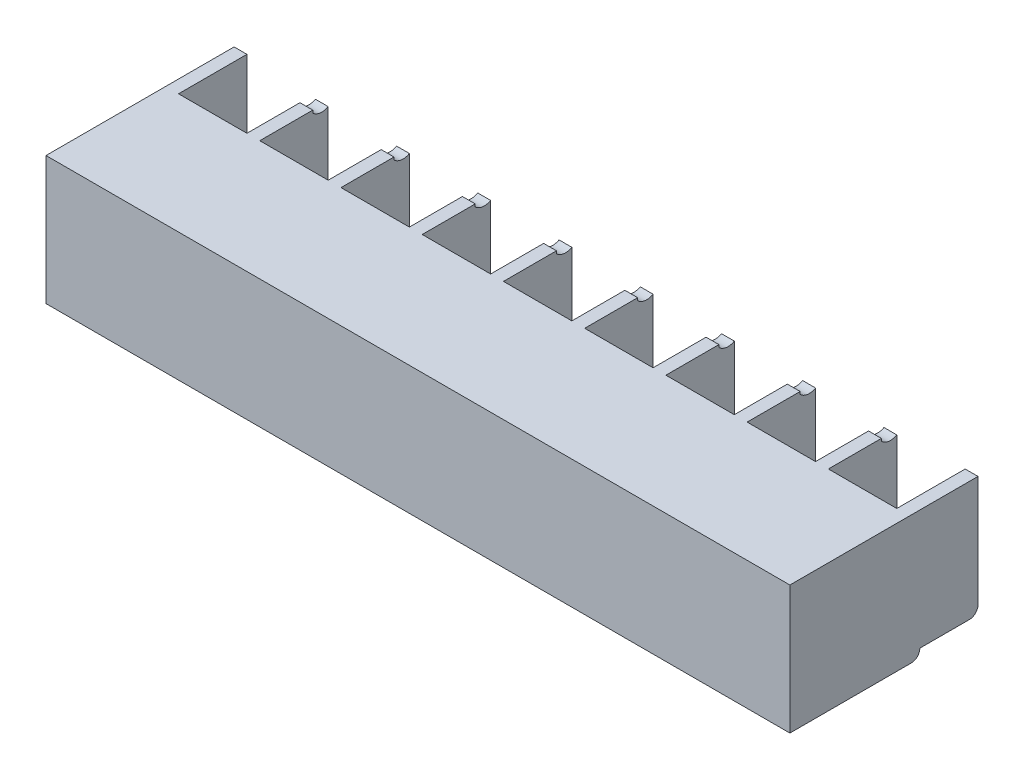
SolidWorks part; units mm, degrees
ref_plane "Спереди" through (0, 0, 0) normal (0, 0, 1) x (1, 0, 0)
ref_plane "Сверху" through (0, 0, 0) normal (0, 1, 0) x (1, 0, 0)
ref_plane "Справа" through (0, 0, 0) normal (1, 0, 0) x (0, 0, -1)
sketch "Эскиз1" plane through (0, 0, 0) normal (0, 0, 1) x (1, 0, 0)
  line L1 (-43.5, -7.5) -> (43.5, -7.5)
  line L2 (-43.5, -7.5) -> (-43.5, 7.5)
  line L3 (-43.5, 7.5) -> (43.5, 7.5)
  line L4 (43.5, -7.5) -> (43.5, 7.5)
  line L5 (-43.5, -7.5) -> (43.5, 7.5) construction
  line L6 (-43.5, 7.5) -> (43.5, -7.5) construction
  point P0 (0, 0)
  dimension "D1" = 87
  dimension "D2" = 15
extrude "Бобышка-Вытянуть1" add sketch "Эскиз1" along normal blind 22
sketch "Эскиз2" plane through (0, 0, 0) normal (0, 0, -1) x (-1, 0, 0)
  line L0 (-42, 7.5) -> (-42, -7.5)
  line L1 (-43.5, 7.5) -> (43.5, 7.5) construction
  line L2 (43.5, -7.5) -> (-43.5, -7.5) construction
  line L3 (-42, -7.5) -> (-34, -7.5)
  line L4 (-34, -7.5) -> (-34, 7.5)
  line L5 (-34, 7.5) -> (-42, 7.5)
  line L6 (-43.5, -7.5) -> (-43.5, 7.5) construction
  line L7 (-32.5, 7.5) -> (-32.5, -7.5)
  line L8 (-24.5, -7.5) -> (-24.5, 7.5)
  line L9 (-24.5, 7.5) -> (-32.5, 7.5)
  line L10 (-32.5, -7.5) -> (-24.5, -7.5)
  line L11 (-23, 7.5) -> (-23, -7.5)
  line L12 (-15, -7.5) -> (-15, 7.5)
  line L13 (-15, 7.5) -> (-23, 7.5)
  line L14 (-23, -7.5) -> (-15, -7.5)
  line L15 (-13.5, 7.5) -> (-13.5, -7.5)
  line L16 (-5.5, -7.5) -> (-5.5, 7.5)
  line L17 (-5.5, 7.5) -> (-13.5, 7.5)
  line L18 (-13.5, -7.5) -> (-5.5, -7.5)
  line L19 (-4, 7.5) -> (-4, -7.5)
  line L20 (4, -7.5) -> (4, 7.5)
  line L21 (4, 7.5) -> (-4, 7.5)
  line L22 (-4, -7.5) -> (4, -7.5)
  line L23 (5.5, 7.5) -> (5.5, -7.5)
  line L24 (13.5, -7.5) -> (13.5, 7.5)
  line L25 (13.5, 7.5) -> (5.5, 7.5)
  line L26 (5.5, -7.5) -> (13.5, -7.5)
  line L27 (15, 7.5) -> (15, -7.5)
  line L28 (23, -7.5) -> (23, 7.5)
  line L29 (23, 7.5) -> (15, 7.5)
  line L30 (15, -7.5) -> (23, -7.5)
  line L31 (24.5, 7.5) -> (24.5, -7.5)
  line L32 (32.5, -7.5) -> (32.5, 7.5)
  line L33 (32.5, 7.5) -> (24.5, 7.5)
  line L34 (24.5, -7.5) -> (32.5, -7.5)
  line L35 (34, 7.5) -> (34, -7.5)
  line L36 (42, -7.5) -> (42, 7.5)
  line L37 (42, 7.5) -> (34, 7.5)
  line L38 (34, -7.5) -> (42, -7.5)
  dimension "D1" = 1.5
  dimension "D2" = 8
  dimension "D3" = 9
extrude "Вырез-Вытянуть1" cut sketch "Эскиз2" against normal blind 8
sketch "Эскиз3" plane through (0, -7.5, 0) normal (0, -1, 0) x (1, 0, 0)
  line L0 (-42, 8) -> (-42, 20.5)
  line L1 (-42, 8) -> (-34, 8)
  line L2 (-34, 8) -> (-34, 20.5)
  line L3 (-34, 20.5) -> (-42, 20.5)
  line L4 (-43.5, 22) -> (43.5, 22) construction
  line L5 (-32.5, 8) -> (-32.5, 20.5)
  line L6 (-32.5, 8) -> (-24.5, 8)
  line L7 (-24.5, 8) -> (-24.5, 20.5)
  line L8 (-24.5, 20.5) -> (-32.5, 20.5)
  line L9 (-23, 8) -> (-23, 20.5)
  line L10 (-23, 8) -> (-15, 8)
  line L11 (-15, 8) -> (-15, 20.5)
  line L12 (-15, 20.5) -> (-23, 20.5)
  line L13 (-13.5, 8) -> (-13.5, 20.5)
  line L14 (-13.5, 8) -> (-5.5, 8)
  line L15 (-5.5, 8) -> (-5.5, 20.5)
  line L16 (-5.5, 20.5) -> (-13.5, 20.5)
  line L17 (-4, 8) -> (-4, 20.5)
  line L18 (-4, 8) -> (4, 8)
  line L19 (4, 8) -> (4, 20.5)
  line L20 (4, 20.5) -> (-4, 20.5)
  line L21 (5.5, 8) -> (5.5, 20.5)
  line L22 (5.5, 8) -> (13.5, 8)
  line L23 (13.5, 8) -> (13.5, 20.5)
  line L24 (13.5, 20.5) -> (5.5, 20.5)
  line L25 (15, 8) -> (15, 20.5)
  line L26 (15, 8) -> (23, 8)
  line L27 (23, 8) -> (23, 20.5)
  line L28 (23, 20.5) -> (15, 20.5)
  line L29 (24.5, 8) -> (24.5, 20.5)
  line L30 (24.5, 8) -> (32.5, 8)
  line L31 (32.5, 8) -> (32.5, 20.5)
  line L32 (32.5, 20.5) -> (24.5, 20.5)
  line L33 (34, 8) -> (34, 20.5)
  line L34 (34, 8) -> (42, 8)
  line L35 (42, 8) -> (42, 20.5)
  line L36 (42, 20.5) -> (34, 20.5)
  dimension "D1" = 1.5
  dimension "D2" = 9
extrude "Вырез-Вытянуть2" cut sketch "Эскиз3" against normal blind 1
sketch "Эскиз4" plane through (0, -7.5, 0) normal (0, -1, 0) x (1, 0, 0)
  line L0 (-34, 6.8) -> (-34, 0)
  line L1 (-34, 20.5) -> (-34, 0) construction
  line L2 (-34, 0) -> (-32.5, 0)
  line L3 (-32.5, 0) -> (-32.5, 6.8)
  line L4 (-32.5, 20.5) -> (-32.5, 0) construction
  line L5 (-32.5, 6.8) -> (-34, 6.8)
  line L6 (-24.5, 6.8) -> (-24.5, 0)
  line L7 (-24.5, 0) -> (-23, 0)
  line L8 (-23, 0) -> (-23, 6.8)
  line L9 (-23, 6.8) -> (-24.5, 6.8)
  line L10 (-15, 6.8) -> (-15, 0)
  line L11 (-15, 0) -> (-13.5, 0)
  line L12 (-13.5, 0) -> (-13.5, 6.8)
  line L13 (-13.5, 6.8) -> (-15, 6.8)
  line L14 (-5.5, 6.8) -> (-5.5, 0)
  line L15 (-5.5, 0) -> (-4, 0)
  line L16 (-4, 0) -> (-4, 6.8)
  line L17 (-4, 6.8) -> (-5.5, 6.8)
  line L18 (4, 6.8) -> (4, 0)
  line L19 (4, 0) -> (5.5, 0)
  line L20 (5.5, 0) -> (5.5, 6.8)
  line L21 (5.5, 6.8) -> (4, 6.8)
  line L22 (13.5, 6.8) -> (13.5, 0)
  line L23 (13.5, 0) -> (15, 0)
  line L24 (15, 0) -> (15, 6.8)
  line L25 (15, 6.8) -> (13.5, 6.8)
  line L26 (23, 6.8) -> (23, 0)
  line L27 (23, 0) -> (24.5, 0)
  line L28 (24.5, 0) -> (24.5, 6.8)
  line L29 (24.5, 6.8) -> (23, 6.8)
  line L30 (32.5, 6.8) -> (32.5, 0)
  line L31 (32.5, 0) -> (34, 0)
  line L32 (34, 0) -> (34, 6.8)
  line L33 (34, 6.8) -> (32.5, 6.8)
  line L34 (42, 6.8) -> (42, 0)
  line L35 (42, 0) -> (43.5, 0)
  line L36 (43.5, 0) -> (43.5, 6.8)
  line L37 (43.5, 6.8) -> (42, 6.8)
  dimension "D1" = 6.8
  dimension "D2" = 9
extrude "Вырез-Вытянуть3" cut sketch "Эскиз4" against normal blind 1
fillet "Скругление1" radius 1 9 edges at (42.75, -7.5, 6.8) (33.25, -7.5, 6.8) (23.75, -7.5, 6.8) (14.25, -7.5, 6.8) (4.75, -7.5, 6.8) (-4.75, -7.5, 6.8) (-14.25, -7.5, 6.8) (-23.75, -7.5, 6.8) (-33.25, -7.5, 6.8)
sketch "Эскиз5" plane through (0, 0, 8) normal (0, 0, -1) x (-1, 0, 0)
  line L0 (-38, 7.5) -> (-38, -9.1228) construction
  line L1 (-34, 7.5) -> (-42, 7.5) construction
  line L2 (-42, 0.5) -> (-34, 0.5) construction
  line L3 (-42, 7.5) -> (-42, -6.5) construction
  line L4 (-34, -6.5) -> (-34, 7.5) construction
  line L5 (-32.125, 6.5) -> (-24.875, 6.5)
  line L6 (-41.625, -5.5) -> (-34.375, -5.5)
  line L7 (-41.625, -5.5) -> (-41.625, 6.5)
  line L8 (-41.625, 6.5) -> (-34.375, 6.5)
  line L9 (-34.375, -5.5) -> (-34.375, 6.5)
  line L10 (-41.625, -5.5) -> (-34.375, 6.5) construction
  line L11 (-41.625, 6.5) -> (-34.375, -5.5) construction
  line L12 (-32.125, -5.5) -> (-32.125, 6.5)
  line L13 (-32.125, -5.5) -> (-24.875, -5.5)
  line L14 (-24.875, -5.5) -> (-24.875, 6.5)
  line L15 (-22.625, 6.5) -> (-15.375, 6.5)
  line L16 (-22.625, -5.5) -> (-22.625, 6.5)
  line L17 (-22.625, -5.5) -> (-15.375, -5.5)
  line L18 (-15.375, -5.5) -> (-15.375, 6.5)
  line L19 (-13.125, 6.5) -> (-5.875, 6.5)
  line L20 (-13.125, -5.5) -> (-13.125, 6.5)
  line L21 (-13.125, -5.5) -> (-5.875, -5.5)
  line L22 (-5.875, -5.5) -> (-5.875, 6.5)
  line L23 (-3.625, 6.5) -> (3.625, 6.5)
  line L24 (-3.625, -5.5) -> (-3.625, 6.5)
  line L25 (-3.625, -5.5) -> (3.625, -5.5)
  line L26 (3.625, -5.5) -> (3.625, 6.5)
  line L27 (5.875, 6.5) -> (13.125, 6.5)
  line L28 (5.875, -5.5) -> (5.875, 6.5)
  line L29 (5.875, -5.5) -> (13.125, -5.5)
  line L30 (13.125, -5.5) -> (13.125, 6.5)
  line L31 (15.375, 6.5) -> (22.625, 6.5)
  line L32 (15.375, -5.5) -> (15.375, 6.5)
  line L33 (15.375, -5.5) -> (22.625, -5.5)
  line L34 (22.625, -5.5) -> (22.625, 6.5)
  line L35 (24.875, 6.5) -> (32.125, 6.5)
  line L36 (24.875, -5.5) -> (24.875, 6.5)
  line L37 (24.875, -5.5) -> (32.125, -5.5)
  line L38 (32.125, -5.5) -> (32.125, 6.5)
  line L39 (34.375, 6.5) -> (41.625, 6.5)
  line L40 (34.375, -5.5) -> (34.375, 6.5)
  line L41 (34.375, -5.5) -> (41.625, -5.5)
  line L42 (41.625, -5.5) -> (41.625, 6.5)
  point P10 (-38, 0.5)
  dimension "D1" = 7.25
  dimension "D2" = 12
  dimension "D3" = 9
extrude "Бобышка-Вытянуть2" add sketch "Эскиз5" along normal blind 2
fillet "Скругление2" radius 2 18 edges at (38, 6.5, 6) (38, -5.5, 6) (28.5, 6.5, 6) (28.5, -5.5, 6) (19, 6.5, 6) (9.5, -5.5, 6) (19, -5.5, 6) (9.5, 6.5, 6) (0, 6.5, 6) (0, -5.5, 6) (-9.5, 6.5, 6) (-9.5, -5.5, 6) (-19, 6.5, 6) (-19, -5.5, 6) (-28.5, 6.5, 6) (-38, 6.5, 6) (-28.5, -5.5, 6) (-38, -5.5, 6)
hole_wizard "Отверстие обработанное метчиком M31" positions "Эскиз7" profile "Эскиз6" tap size "M3" standard "ISO"
sketch "Эскиз7" plane through (0, 0, 6) normal (0, 0, -1) x (-1, 0, 0)
  line L0 (43.5, 7.5) -> (43.5, -7.5) construction
  line L1 (42, 7.5) -> (34, 7.5) construction
  point P0 (38, 0)
  dimension "D1" = 5.5
  dimension "D2" = 7.5
sketch "Эскиз6" plane through (-38, 0, 6) normal (1, 0, 0) x (0, 1, 0)
  line L0 (0, 0) -> (0, 6.2511)
  line L1 (0, 6.2511) -> (1.25, 5.5)
  line L2 (1.25, 5.5) -> (1.25, 0)
  line L5 (1.25, 0) -> (0, 0)
  line L10 (0, 6.2511) -> (-1.25, 5.5) construction
  line L11 (0, -6.35) -> (0, 107.95) construction
  dimension "Диаметр сверла" = 2.5
  dimension "Глубина сверла" = 5.5
  dimension "Угол заточки сверла" = 118
cosmetic thread "Отверстие резьбы1" parameters "D1"=3, "D2"=3
pattern_linear "Линейный массив1" count 9 spacing 9.5 along (1, 0, 0) of "Отверстие обработанное метчиком M31"
fillet "Скругление3" radius 1 2 edges at (42.75, -6.5, 0) (-42.75, -7.5, 0)
fillet "Скругление4" radius 2 8 edges at (33.25, -6.5, 0) (23.75, -6.5, 0) (14.25, -6.5, 0) (4.75, -6.5, 0) (-4.75, -6.5, 0) (-14.25, -6.5, 0) (-23.75, -6.5, 0) (-33.25, -6.5, 0)
sketch "Эскиз8" plane through (0, 0, 0) normal (1, 0, 0) x (0, 0, -1)
  line L0 (-1.8, 7.5) -> (0.3213, 7.5)
  line L1 (-22, 7.5) -> (0, 7.5) construction
  line L2 (-1.8, 7.5) -> (-1.8, 7.2)
  line L5 (0.3213, 7.5) -> (0.3213, 7.2)
  line L6 (-22, -7.5) -> (-22, 7.5) construction
  arc A0 (-1.8, 7.2) -> (0.3213, 7.2) centre (-0.7393, 8.2607) ccw
  dimension "D2" = 2.1213
  dimension "D1" = 1.5
  dimension "D3" = 0.3
  dimension "D4" = 22.3213
  dimension "D5" = 0.3
extrude "Вырез-Вытянуть4" cut sketch "Эскиз8" against normal mid plane 72
